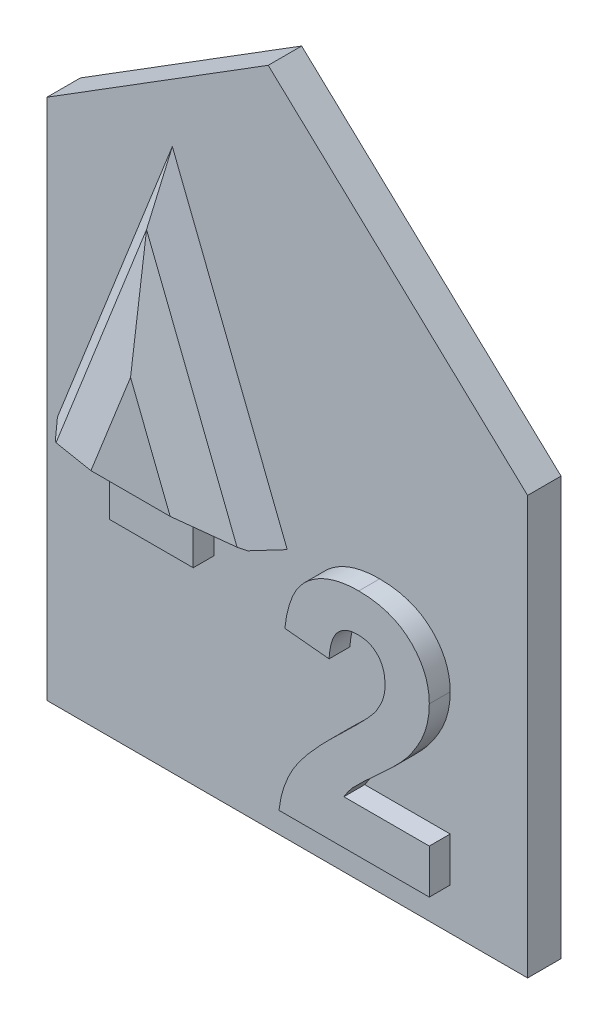
SolidWorks part; units mm, degrees
ref_plane "Přední rovina" through (0, 0, 0) normal (0, 0, 1) x (1, 0, 0)
ref_plane "Horní rovina" through (0, 0, 0) normal (0, 1, 0) x (1, 0, 0)
ref_plane "Pravá rovina" through (0, 0, 0) normal (1, 0, 0) x (0, 0, -1)
sketch "Skica1" plane through (0, 0, 0) normal (0, 0, 1) x (1, 0, 0)
  line L0 (-66.5051, 0) -> (66.5051, 0) construction
  line L1 (0, 0) -> (0, 20)
  line L2 (0, 20) -> (-12.4128, 31.6156)
  line L3 (-12.4128, 31.6156) -> (-23, 25)
  line L4 (-23, 25) -> (-23, 0)
  line L5 (-23, 0) -> (0, 0)
  dimension "D1" = 23
  dimension "D2" = 25
  dimension "D3" = 20
  dimension "D4" = 17
  dimension "D5" = 122
extrude "Přidat vysunutím5" add sketch "Skica1" along normal blind 1.6
sketch "Skica2" plane through (0, 0, 1.6) normal (0, 0, 1) x (1, 0, 0)
  line L0 (-23, 10) -> (0, 10) construction
  line L1 (-23, 25) -> (-23, 0) construction
  line L2 (0, 0) -> (0, 20) construction
  line L3 (-3, 0) -> (-3, 22.8073) construction
  line L4 (-23, 0) -> (0, 0) construction
  line L5 (0, 20) -> (-12.4128, 31.6156) construction
  line L6 (-23, 2) -> (-3, 2) construction
  line L7 (-19, 10) -> (-15, 10)
  line L8 (-15, 10) -> (-15, 12)
  line L9 (-15, 12) -> (-11.5025, 12)
  line L10 (-11.5025, 12) -> (-17, 25.9563)
  line L11 (-17, 25.9563) -> (-17, 10)
  line L12 (-19, 10) -> (-19, 12)
  line L13 (-19, 12) -> (-22.4975, 12)
  line L14 (-22.4975, 12) -> (-17, 25.9563)
  line L15 (-19, 12) -> (-15, 12)
  dimension "D1" = 10
  dimension "D2" = 3
  dimension "D3" = 2
  dimension "D4" = 15
  dimension "D5" = 4
  dimension "D6" = 2
  dimension "D7" = 4
  dimension "D8" = 43
extrude "Přidat vysunutím6" add sketch "Skica2" along normal blind 2 contours L11 L15 L9 L10 | L13 L15 L11 L14 region at (-18.8325, 16.6521, 1.6) region at (-15.1675, 16.6521, 1.6)
extrude "Přidat vysunutím7" add sketch "Skica2<7>" along normal blind 1 contours L15 L11 L7 L8 | L15 L12 L7 L11 region at (-18, 11, 1.6) region at (-16, 11, 1.6)
sketch "Skica2<7>" plane through (0, 0, 1.6) normal (0, 0, 1) x (1, 0, 0) same geometry as "Skica2"
sketch "Skica3" plane through (0, 0, 1.6) normal (0, 0, 1) x (1, 0, 0)
  line L0 (-3, 22.8073) -> (-3, 0) construction
  line L3 (0, 20) -> (-12.4128, 31.6156) construction
  line L4 (-23, 0) -> (0, 0) construction
  line L5 (-23, 2) -> (-3, 2) construction
  line L6 (-23, 25) -> (-23, 0) construction
  line L7 (0, 0) -> (0, 20) construction
  text T0 "2" font "Arial" height 11
  dimension "D1" = 2
  dimension "D2" = 3
extrude "Přidat vysunutím8" add sketch "Skica3" along normal blind 1
chamfer "Zkosení5" distance 2 angle 40 1 edges at (-14.2512, 18.9781, 3.6) first distance on face at (-14.2512, 18.9781, 2.6)
chamfer "Zkosení8" distance 2 angle 40 1 edges at (-20.1997, 17.8334, 3.6) first distance on face at (-19.9742, 18.4058, 2.6)
chamfer "Zkosení12" distance 1 angle 30 3 edges at (-17, 12, 3.6) (-18.8469, 16.6886, 3.6) (-15.1531, 16.6886, 3.6) first distance on face at (-17, 12, 2.35) first distance on face at (-19.2978, 17.8334, 2.6) first distance on face at (-14.7022, 17.8334, 2.6)
